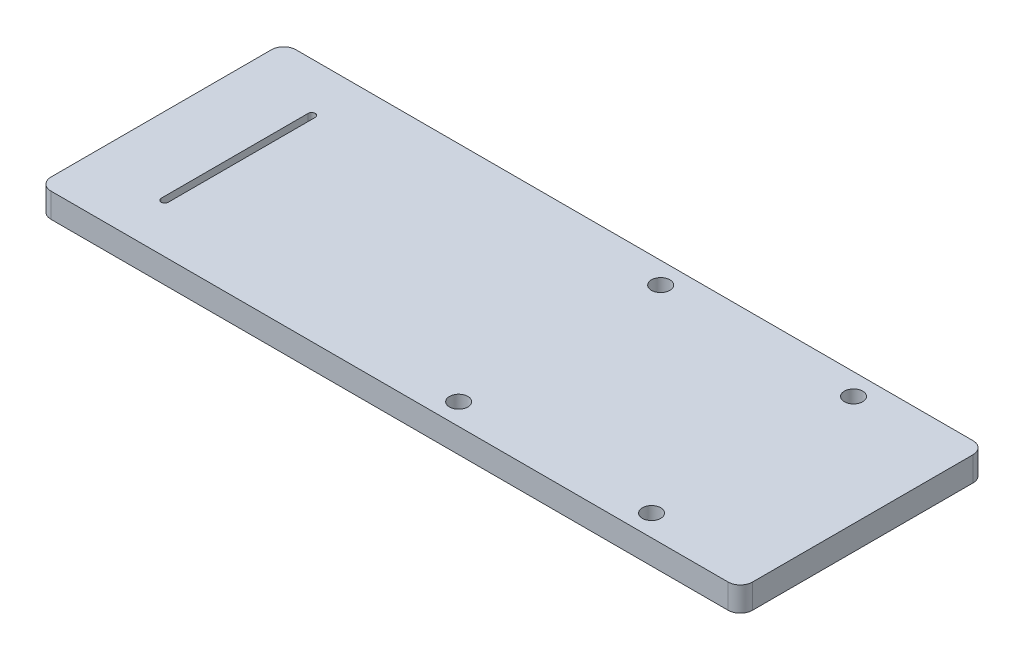
SolidWorks part; units mm, degrees
material "6061 Alloy"
ref_plane "Front Plane" through (0, 0, 0) normal (0, 0, 1) x (1, 0, 0)
ref_plane "Top Plane" through (0, 0, 0) normal (0, 1, 0) x (1, 0, 0)
ref_plane "Right Plane" through (0, 0, 0) normal (1, 0, 0) x (0, 0, -1)
sketch "Sketch1" plane through (0, 0, 0) normal (0, 1, 0) x (1, 0, 0)
  line L1 (-181.9, -63.5) -> (181.9, -63.5)
  line L2 (-181.9, -63.5) -> (-181.9, 63.5)
  line L3 (-181.9, 63.5) -> (181.9, 63.5)
  line L4 (181.9, -63.5) -> (181.9, 63.5)
  line L5 (-181.9, -63.5) -> (181.9, 63.5) construction
  line L6 (-181.9, 63.5) -> (181.9, -63.5) construction
  point P0 (0, 0)
  dimension "D1" = 127
  dimension "D2" = 363.8
extrude "Boss-Extrude1" add sketch "Sketch1" along normal blind 12.7
fillet "Fillet1" radius 6.35 4 edges at (-181.9, 6.35, -63.5) (181.9, 6.35, -63.5) (181.9, 6.35, 63.5) (-181.9, 6.35, 63.5)
sketch "Sketch2" plane through (0, 12.7, 0) normal (0, 1, 0) x (1, 0, 0)
  line L0 (-181.9, 0) -> (181.9, 0) construction
  line L3 (-181.9, 57.15) -> (-181.9, -57.15) construction
  line L4 (181.9, -57.15) -> (181.9, 57.15) construction
  line L5 (0, 63.5) -> (0, -63.5) construction
  line L6 (175.55, 63.5) -> (-175.55, 63.5) construction
  line L7 (-175.55, -63.5) -> (175.55, -63.5) construction
  circle A0 centre (24.73, 52.3748) radius 4.7752
  circle A1 centre (24.73, -52.3748) radius 4.7752
  circle A2 centre (124.75, -52.3748) radius 4.7752
  circle A3 centre (124.75, 52.3748) radius 4.7752
  point P14 (24.73, 57.15)
  point P15 (0, 0)
  point P22 (0, 0)
  dimension "D1" = 100.02
  dimension "D4" = 9.5504
  dimension "D2" = 6.35
  dimension "D3" = 57.15
  dimension "D5" = 57.15
extrude "Cut-Extrude1" cut sketch "Sketch2" against normal through all
sketch "Sketch3" plane through (0, 0, 0) normal (0, -1, 0) x (1, 0, 0)
  line L0 (-141.9753, 38.1) -> (-141.9753, -38.1) construction
  line L2 (-140.1464, 38.1) -> (-140.1464, -38.1)
  line L3 (-143.8041, 38.1) -> (-143.8041, -38.1)
  line L4 (-181.9, 0) -> (181.9, 0) construction
  line L5 (-181.9, -57.15) -> (-181.9, 57.15) construction
  line L6 (181.9, 57.15) -> (181.9, -57.15) construction
  arc A0 (-140.1464, 38.1) -> (-143.8041, 38.1) centre (-141.9753, 38.1) ccw
  arc A1 (-143.8041, -38.1) -> (-140.1464, -38.1) centre (-141.9753, -38.1) ccw
  point P4 (-141.9753, 0)
  dimension "D1" = 0
  dimension "D2" = 76.2
extrude "Cut-Extrude2" cut sketch "Sketch3" against normal up to next
